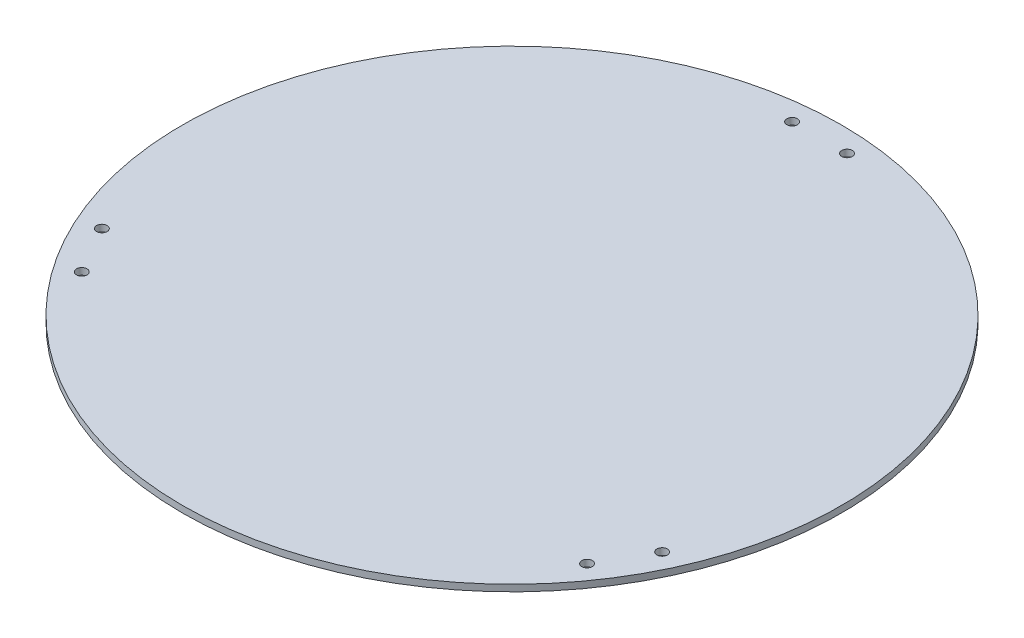
SolidWorks part; units mm, degrees
ref_plane "Front Plane" through (0, 0, 0) normal (0, 0, 1) x (1, 0, 0)
ref_plane "Top Plane" through (0, 0, 0) normal (0, 1, 0) x (1, 0, 0)
ref_plane "Right Plane" through (0, 0, 0) normal (1, 0, 0) x (0, 0, -1)
sketch "Sketch1" plane through (0, 0, 0) normal (0, 1, 0) x (1, 0, 0)
  line L0 (0, 0) -> (0, 140) construction
  line L1 (0, 140) -> (0, 150) construction
  line L2 (-12.5, 140) -> (12.5, 140) construction
  circle A0 centre (0, 0) radius 150
  circle A1 centre (12.5, 140) radius 2.4
  circle A2 centre (-12.5, 140) radius 2.4
  circle A3 centre (127.4936, -59.1747) radius 2.4
  circle A4 centre (114.9936, -80.8253) radius 2.4
  circle A5 centre (-114.9936, -80.8253) radius 2.4
  circle A6 centre (-127.4936, -59.1747) radius 2.4
  point P9 (0, 140)
  point P21 (0, 0)
  dimension "D1" = 300
  dimension "D2" = 3
  dimension "D4" = 4.8
  dimension "D3" = 25
  dimension "D5" = 140
extrude "Boss-Extrude1" add sketch "Sketch1" along normal blind 3
ref_axis "Axis1" through (0, -0.15, 0) along (0, 1, 0)
ref_point "Point2"
